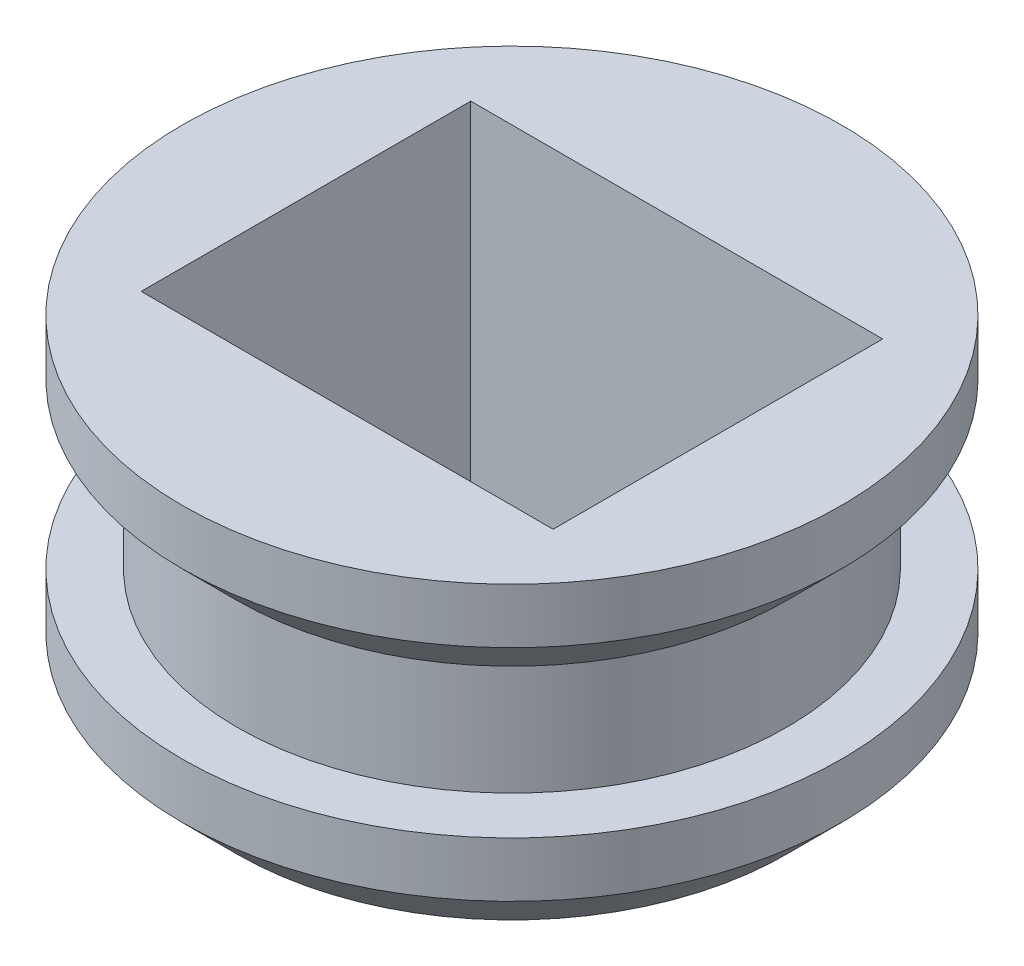
SolidWorks part; units mm, degrees
ref_plane "Front Plane" through (0, 0, 0) normal (0, 0, 1) x (1, 0, 0)
ref_plane "Top Plane" through (0, 0, 0) normal (0, 1, 0) x (1, 0, 0)
ref_plane "Right Plane" through (0, 0, 0) normal (1, 0, 0) x (0, 0, -1)
sketch "Sketch1" plane through (0, 0, 0) normal (0, 1, 0) x (1, 0, 0)
  circle A0 centre (0, 0) radius 5
  dimension "D1" = 10
extrude "Boss-Extrude1" add sketch "Sketch1" against normal blind 2
sketch "Sketch2" plane through (0, 0, 0) normal (0, 1, 0) x (1, 0, 0)
  circle A0 centre (0, 0) radius 6
  dimension "D1" = 12
extrude "Boss-Extrude2" add sketch "Sketch2" along normal blind 2
extrude "Boss-Extrude3" add sketch "Sketch2<2>" against normal blind 2 from surface starting at face at (0, -2, 5)
sketch "Sketch2<2>" plane through (0, 0, 0) normal (0, 1, 0) x (1, 0, 0) same geometry as "Sketch2"
chamfer "Chamfer1" distance 1 angle 45 2 edges at (0, 0, 6) (0, -4, 6)
sketch "Sketch3" plane through (0, -4, 0) normal (0, -1, 0) x (1, 0, 0)
  line L1 (-3.75, -3) -> (3.75, -3)
  line L2 (-3.75, -3) -> (-3.75, 3)
  line L3 (-3.75, 3) -> (3.75, 3)
  line L4 (3.75, -3) -> (3.75, 3)
  line L5 (-3.75, -3) -> (3.75, 3) construction
  line L6 (-3.75, 3) -> (3.75, -3) construction
  point P0 (0, 0)
  dimension "D1" = 7.5
  dimension "D2" = 6
extrude "Cut-Extrude1" cut sketch "Sketch3" against normal through all
